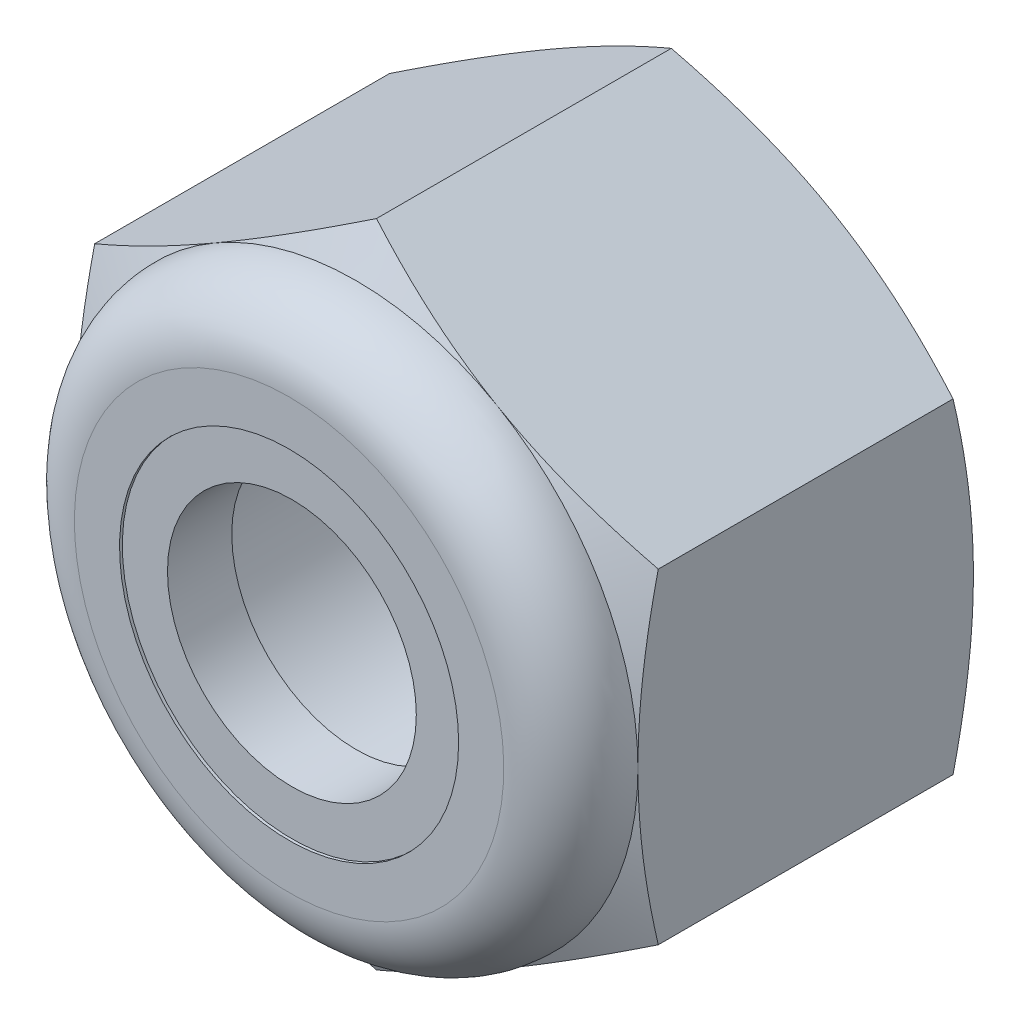
SolidWorks part; units mm, degrees
material "Alloy Steel"
ref_plane "Front Plane" through (0, 0, 0) normal (0, 0, 1) x (1, 0, 0)
ref_plane "Top Plane" through (0, 0, 0) normal (0, 1, 0) x (1, 0, 0)
ref_plane "Right Plane" through (0, 0, 0) normal (1, 0, 0) x (0, 0, -1)
sketch "Sketch1" plane through (0, 0, 0) normal (0, 0, 1) x (1, 0, 0)
  line L1 (0, 4.0415) -> (-3.5, 2.0207)
  line L2 (-3.5, 2.0207) -> (-3.5, -2.0207)
  line L3 (-3.5, -2.0207) -> (0, -4.0415)
  line L4 (0, -4.0415) -> (3.5, -2.0207)
  line L5 (3.5, -2.0207) -> (3.5, 2.0207)
  line L6 (3.5, 2.0207) -> (0, 4.0415)
  circle A0 centre (0, 0) radius 3.5 construction
  circle A1 centre (0, 0) radius 2
  point P10 (0, -2)
  point P11 (0, 2)
  point P12 (0, 3.5)
  dimension "Thread Size" = 4
  dimension "Width" = 7
sketch "Sketch2" plane through (0, 0, 0) normal (1, 0, 0) x (0, 0, -1)
  line L0 (2.5, 0) -> (-2.5, 0) construction
  line L1 (-2.5, 2) -> (2.5, 2) construction
  line L2 (-2.465, -2.106) -> (-3.77, -2.106) construction
  line L3 (-3.1563, 2.0758) -> (-2.4563, 2.0758) construction
  line L4 (-2.4563, 2.0758) -> (-2.8063, 1.4696) construction
  line L5 (-2.8063, 1.4696) -> (-3.1563, 2.0758) construction
  line L6 (-3.1125, 2) -> (-2.5, 2) construction
  line L7 (-2.85, 1.5453) -> (-2.7625, 1.5453) construction
  line L8 (-2.8063, 1.5453) -> (-2.8063, 1.4696) construction
  line L9 (-2.8063, 2) -> (-2.8063, 2.0758) construction
  line L10 (-2.4781, 2.0379) -> (-3.1344, 2.0379)
  line L11 (-3.1344, 2.0379) -> (-2.85, 1.5453)
  line L12 (-2.85, 1.5453) -> (-2.7625, 1.5453)
  line L13 (-2.7625, 1.5453) -> (-2.4781, 2.0379)
  line L14 (2.5, 0) -> (3.77, 0)
  line L15 (3.77, 0) -> (3.77, 5.3115)
  line L16 (0, 5.3115) -> (0, 4.0415) construction
  line L17 (0, 4.0415) -> (0, 2.0207) construction
  line L18 (2.5, 3.5) -> (-1.6667, 3.5) construction
  line L19 (-2.85, -1.5453) -> (-2.7625, -1.5453) construction
  line L20 (2.5, 3.5) -> (2.5, 0)
  line L21 (2.2475, 4.0415) -> (-1.4142, 4.0415)
  line L22 (2.5, 3.5) -> (2.2475, 4.0415)
  line L23 (-2.5, 0) -> (-2.5, 2.6667) construction
  line L24 (-1.6667, 3.5) -> (-1.4142, 4.0415)
  line L25 (3.77, 5.3115) -> (-3.77, 5.3115)
  line L26 (-2.5, 2.6667) -> (-3.77, 2.6667)
  line L27 (-3.77, 2.6667) -> (-3.77, 5.3115)
  line L28 (-2.465, 2.6667) -> (-2.465, 1.5453) construction
  line L29 (-2.465, 2.106) -> (-3.77, 2.106)
  line L30 (-3.77, 2.106) -> (-3.77, 0)
  line L31 (-3.77, 0) -> (-1.6667, 0)
  line L32 (-1.6667, 0) -> (-1.6667, 3.465)
  line L33 (-2.465, 2.106) -> (-2.465, 2.6667)
  arc A0 (-1.6667, 3.5) -> (-2.5, 2.6667) centre (-1.6667, 2.6667) ccw
  arc A1 (-1.6667, 3.465) -> (-2.465, 2.6667) centre (-1.6667, 2.6667) ccw
  point P4 (0, 0)
  point P18 (-2.8063, 2.0379)
  point P22 (-2.8063, 2.0379)
  point P33 (0, 4.0415)
  point P48 (-3.77, -2.106)
  point P51 (-2.85, -1.5453)
  dimension "Height" = 5
  dimension "Pitch" = 0.7
  dimension "D1" = 0.0875
  dimension "D2" = 1.27
  dimension "D3" = 25
  dimension "D4" = 0.8333
  dimension "D5" = 25
  dimension "D6" = 0.035
sketch "Sketch3" plane through (0, 0, 0) normal (0, 0, 1) x (1, 0, 0)
  line L0 (0, -4.0415) -> (3.5, -2.0207) construction
  line L1 (3.5, -2.0207) -> (3.5, 2.0207) construction
  line L2 (3.5, 2.0207) -> (0, 4.0415) construction
  line L3 (0, 4.0415) -> (-3.5, 2.0207) construction
  line L4 (-3.5, 2.0207) -> (-3.5, -2.0207) construction
  line L5 (-3.5, -2.0207) -> (0, -4.0415) construction
  line L6 (0, -4.0415) -> (3.5, -2.0207)
  line L7 (3.5, -2.0207) -> (3.5, 2.0207)
  line L8 (3.5, 2.0207) -> (0, 4.0415)
  line L9 (0, 4.0415) -> (-3.5, 2.0207)
  line L10 (-3.5, 2.0207) -> (-3.5, -2.0207)
  line L11 (-3.5, -2.0207) -> (0, -4.0415)
  circle A0 centre (0, 0) radius 2 construction
  circle A1 centre (0, 0) radius 2
extrude "Boss-Extrude1" add sketch "Sketch3" along normal mid plane 5
sketch "Sketch4" plane through (0, 0, 0) normal (1, 0, 0) x (0, 0, -1)
  line L0 (3.77, 5.3115) -> (-3.77, 5.3115) construction
  line L1 (-3.77, 2.6667) -> (-3.77, 5.3115) construction
  line L2 (-2.5, 2.6667) -> (-3.77, 2.6667) construction
  line L3 (-1.6667, 3.5) -> (-1.4142, 4.0415) construction
  line L4 (2.2475, 4.0415) -> (-1.4142, 4.0415) construction
  line L5 (2.5, 3.5) -> (2.2475, 4.0415) construction
  line L6 (2.5, 3.5) -> (2.5, 0) construction
  line L7 (2.5, 0) -> (3.77, 0) construction
  line L8 (3.77, 0) -> (3.77, 5.3115) construction
  line L9 (-3.77, 2.106) -> (-3.77, 0) construction
  line L10 (-3.77, 0) -> (-1.6667, 0) construction
  line L11 (-1.6667, 0) -> (-1.6667, 3.465) construction
  line L12 (-2.465, 2.106) -> (-2.465, 2.6667) construction
  line L13 (-2.465, 2.106) -> (-3.77, 2.106) construction
  line L14 (3.77, 5.3115) -> (-3.77, 5.3115)
  line L15 (-3.77, 2.6667) -> (-3.77, 5.3115)
  line L16 (-2.5, 2.6667) -> (-3.77, 2.6667)
  line L17 (-1.6667, 3.5) -> (-1.4142, 4.0415)
  line L18 (2.2475, 4.0415) -> (-1.4142, 4.0415)
  line L19 (2.5, 3.5) -> (2.2475, 4.0415)
  line L20 (2.5, 3.5) -> (2.5, 0)
  line L21 (2.5, 0) -> (3.77, 0)
  line L22 (3.77, 0) -> (3.77, 5.3115)
  line L23 (-3.77, 2.106) -> (-3.77, 0)
  line L24 (-3.77, 0) -> (-1.6667, 0)
  line L25 (-1.6667, 0) -> (-1.6667, 3.465)
  line L26 (-2.465, 2.106) -> (-2.465, 2.6667)
  line L27 (-2.465, 2.106) -> (-3.77, 2.106)
  arc A0 (-1.6667, 3.5) -> (-2.5, 2.6667) centre (-1.6667, 2.6667) ccw construction
  arc A1 (-1.6667, 3.465) -> (-2.465, 2.6667) centre (-1.6667, 2.6667) ccw construction
  arc A2 (-1.6667, 3.5) -> (-2.5, 2.6667) centre (-1.6667, 2.6667) ccw
  arc A3 (-1.6667, 3.465) -> (-2.465, 2.6667) centre (-1.6667, 2.6667) ccw
revolve "Cut-Revolve1" cut sketch "Sketch4" angle 360 about L0
sketch "Sketch5" plane through (0, 0, 0) normal (1, 0, 0) x (0, 0, -1)
  line L0 (-2.465, 2.6667) -> (-2.465, 1.5453) construction
  line L1 (-1.6667, 0) -> (-1.6667, 3.465) construction
  line L2 (-2.465, 2.6667) -> (-2.465, 1.5453)
  line L3 (-1.6667, 1.5453) -> (-1.6667, 3.465)
  line L4 (-2.465, 1.5453) -> (-1.6667, 1.5453)
  arc A0 (-1.6667, 3.465) -> (-2.465, 2.6667) centre (-1.6667, 2.6667) ccw construction
  arc A1 (-1.6667, 3.465) -> (-2.465, 2.6667) centre (-1.6667, 2.6667) ccw
revolve "Revolve1" add sketch "Sketch5" angle 360 about L0
sketch "Sketch6" [suppressed] plane through (0, 0, 2.5) normal (0, 0, 1) x (1, 0, 0)
  circle A0 centre (0, 0) radius 2 construction
  circle A1 centre (0, 0) radius 2
curve "Helix/Spiral1" [suppressed] pitch 0.7 height 5.7 turns 8.1429
sketch "Sketch7" [suppressed] plane through (0, 0, 0) normal (1, 0, 0) x (0, 0, -1)
  line L0 (-3.1344, 2.0379) -> (-2.85, 1.5453) construction
  line L1 (-2.85, 1.5453) -> (-2.7625, 1.5453) construction
  line L2 (-2.7625, 1.5453) -> (-2.4781, 2.0379) construction
  line L3 (-2.4781, 2.0379) -> (-3.1344, 2.0379) construction
  line L4 (-3.1344, 2.0379) -> (-2.85, 1.5453)
  line L5 (-2.85, 1.5453) -> (-2.7625, 1.5453)
  line L6 (-2.7625, 1.5453) -> (-2.4781, 2.0379)
  line L7 (-2.4781, 2.0379) -> (-3.1344, 2.0379)
sweep "Sweep1" [suppressed] add profiles "Sketch7" path "Helix/Spiral1"
sketch "Sketch8" [suppressed] plane through (0, 0, -2.5) normal (0, 0, -1) x (-1, 0, 0)
  circle A2 centre (0, 0) radius 2.0379
  point P2 (0, 2.0379)
extrude "Cut-Extrude1" [suppressed] cut sketch "Sketch8" along normal through all and the other way through all draft 60
sketch "Sketch9" [suppressed] plane through (0, 0, 1.6667) normal (0, 0, 1) x (1, 0, 0)
  circle A2 centre (0, 0) radius 2.0379
  circle A3 centre (0, 0) radius 1.5453 construction
  point P2 (0, 2.0379)
  point P4 (0, 1.5453)
extrude "Cut-Extrude2" [suppressed] cut sketch "Sketch9" along normal through all and the other way through all draft 60
equation "\"D1@Sketch2\" = \"Pitch@Sketch2\" / 8"
equation "\"D4@Sketch2\"=\"Height@Sketch2\"/6"
equation "\"D1@Boss-Extrude1\"=\"Height@Sketch2\""
equation "\"D3@Helix/Spiral1\"=\"Height@Sketch2\"+\"Pitch@Sketch2\""
equation "\"D4@Helix/Spiral1\"=\"Pitch@Sketch2\""
equation "\"D6@Sketch2\"=\"Pitch@Sketch2\"*0.05"
